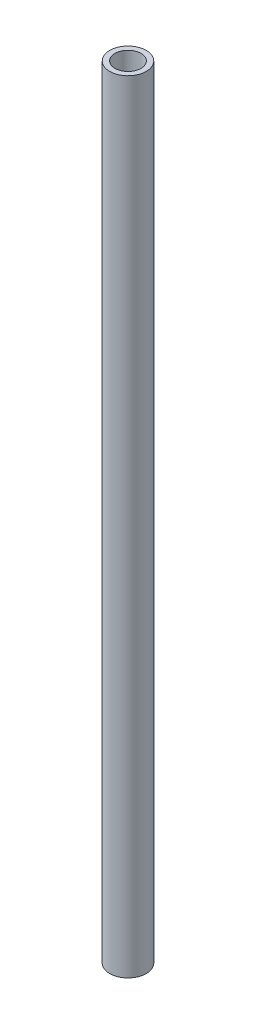
SolidWorks part; units mm, degrees
ref_plane "Front Plane" through (0, 0, 0) normal (0, 0, 1) x (1, 0, 0)
ref_plane "Top Plane" through (0, 0, 0) normal (0, 1, 0) x (1, 0, 0)
ref_plane "Right Plane" through (0, 0, 0) normal (1, 0, 0) x (0, 0, -1)
sketch "Sketch1" plane through (0, 0, 0) normal (0, 1, 0) x (1, 0, 0)
  circle A0 centre (0, 0) radius 2.5
  circle A1 centre (0, 0) radius 3.5
  dimension "D1" = 5
  dimension "D2" = 7
extrude "Boss-Extrude1" add sketch "Sketch1" along normal blind 150
